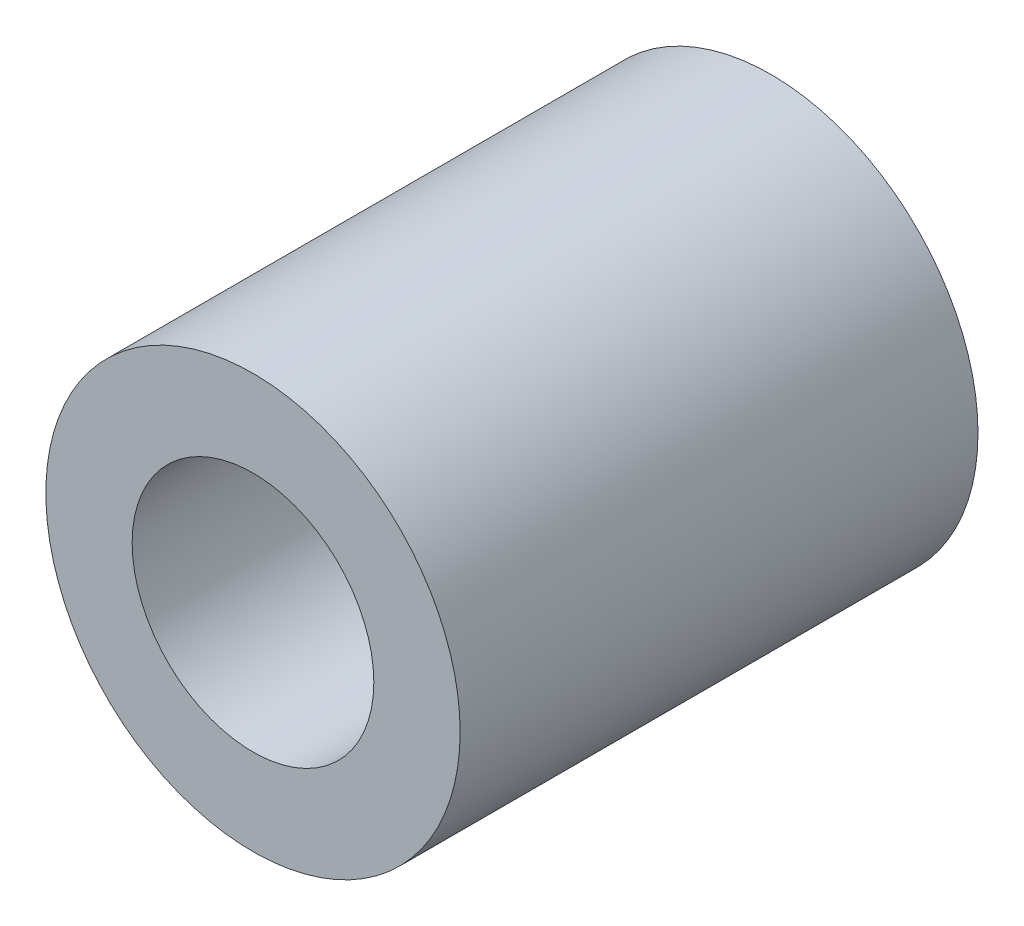
SolidWorks part; units mm, degrees
ref_plane "前视基准面" through (0, 0, 0) normal (0, 0, 1) x (1, 0, 0)
ref_plane "上视基准面" through (0, 0, 0) normal (0, 1, 0) x (1, 0, 0)
ref_plane "右视基准面" through (0, 0, 0) normal (1, 0, 0) x (0, 0, -1)
sketch "草图1" plane through (0, 0, 0) normal (0, 0, 1) x (1, 0, 0)
  circle A0 centre (0, 0) radius 3.5
  circle A1 centre (0, 0) radius 6
extrude "凸台-拉伸1" add sketch "草图1" along normal blind 15
